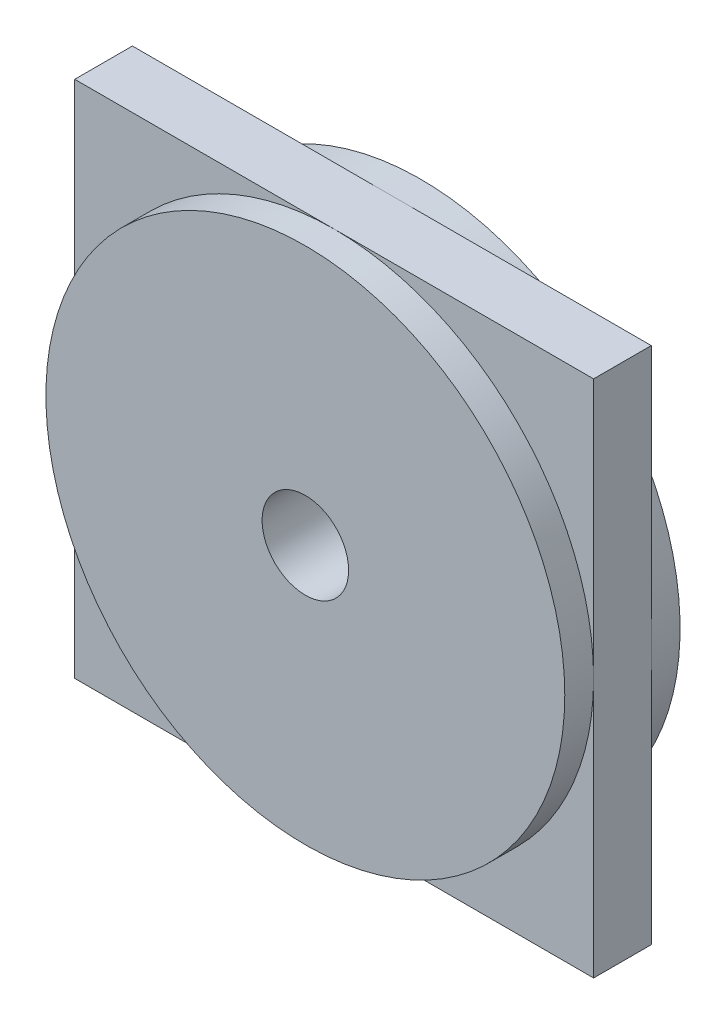
SolidWorks part; units mm, degrees
ref_plane "Спереди" through (0, 0, 0) normal (0, 0, 1) x (1, 0, 0)
ref_plane "Сверху" through (0, 0, 0) normal (0, 1, 0) x (1, 0, 0)
ref_plane "Справа" through (0, 0, 0) normal (1, 0, 0) x (0, 0, -1)
sketch "Эскиз1" plane through (0, 0, 0) normal (0, 0, 1) x (1, 0, 0)
  line L1 (9, 9) -> (-9, 9)
  line L2 (9, 9) -> (9, -9)
  line L3 (9, -9) -> (-9, -9)
  line L4 (-9, 9) -> (-9, -9)
  line L5 (9, 9) -> (-9, -9) construction
  line L6 (9, -9) -> (-9, 9) construction
  point P0 (0, 0)
  dimension "D1" = 18
  dimension "D2" = 18
extrude "Бобышка-Вытянуть1" add sketch "Эскиз1" along normal blind 2
sketch "Эскиз2" plane through (0, 0, 0) normal (0, 0, -1) x (-1, 0, 0)
  circle A0 centre (0, 0) radius 9
extrude "Бобышка-Вытянуть2" add sketch "Эскиз2" along normal blind 1
sketch "Эскиз3" plane through (0, 0, 2) normal (0, 0, 1) x (1, 0, 0)
  circle A0 centre (0, 0) radius 9
extrude "Бобышка-Вытянуть3" add sketch "Эскиз3" along normal blind 1
sketch "Эскиз4" plane through (0, 0, 3) normal (0, 0, 1) x (1, 0, 0)
  circle A0 centre (0, 0) radius 1.5
extrude "Вырез-Вытянуть1" cut sketch "Эскиз4" against normal through all
